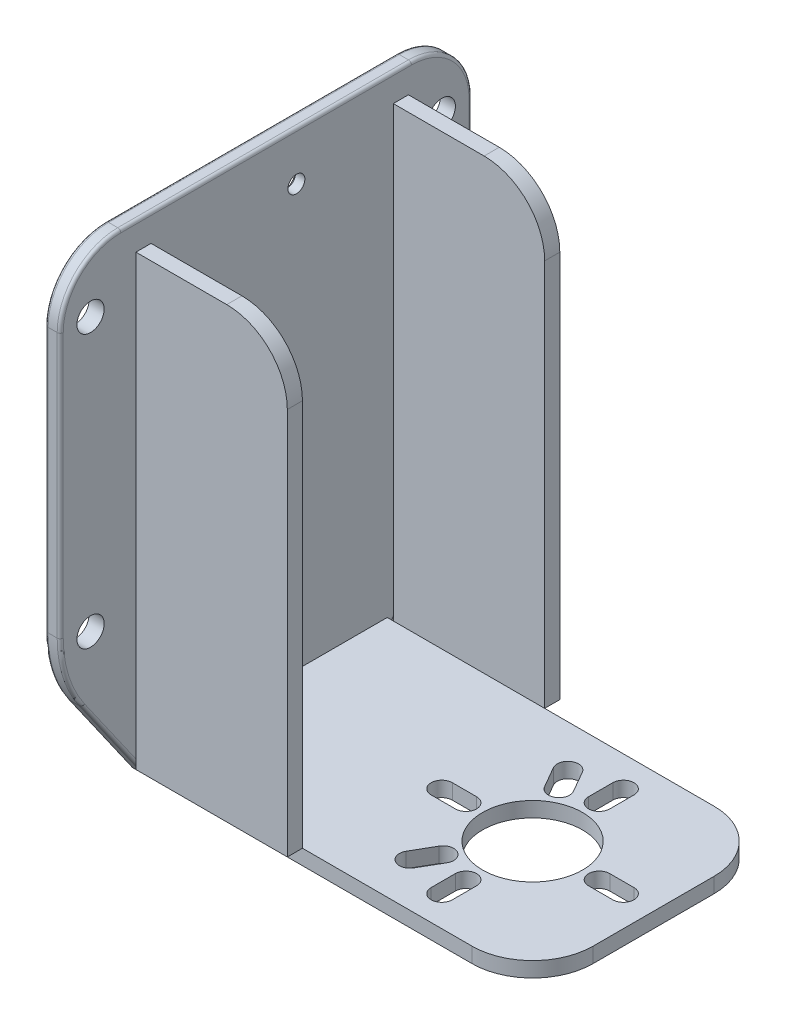
SolidWorks part; units mm, degrees
ref_plane "前视基准面" through (0, 0, 0) normal (0, 0, 1) x (1, 0, 0)
ref_plane "上视基准面" through (0, 0, 0) normal (0, 1, 0) x (1, 0, 0)
ref_plane "右视基准面" through (0, 0, 0) normal (1, 0, 0) x (0, 0, -1)
sketch "草图1" plane through (0, 0, 0) normal (0, 1, 0) x (1, 0, 0)
  line L0 (-53.6479, 52.8766) -> (-53.6479, 12.8766) construction
  line L1 (-77.6479, 52.8766) -> (-13.6479, 52.8766)
  line L2 (-77.6479, 52.8766) -> (-77.6479, 12.8766)
  line L3 (-77.6479, 12.8766) -> (-13.6479, 12.8766)
  line L4 (-13.6479, 52.8766) -> (-13.6479, 12.8766)
  line L5 (-18.6479, 32.8766) -> (-22.6479, 32.8766) construction
  line L6 (-18.6479, 31.1266) -> (-22.6479, 31.1266)
  line L7 (-18.6479, 34.6266) -> (-22.6479, 34.6266)
  line L8 (-33.6479, 17.8766) -> (-33.6479, 21.8766) construction
  line L9 (-35.3979, 17.8766) -> (-35.3979, 21.8766)
  line L10 (-31.8979, 17.8766) -> (-31.8979, 21.8766)
  line L11 (-48.6479, 32.8766) -> (-44.6479, 32.8766) construction
  line L12 (-48.6479, 34.6266) -> (-44.6479, 34.6266)
  line L13 (-48.6479, 31.1266) -> (-44.6479, 31.1266)
  line L14 (-33.6479, 47.8766) -> (-33.6479, 43.8766) construction
  line L15 (-31.8979, 47.8766) -> (-31.8979, 43.8766)
  line L16 (-35.3979, 47.8766) -> (-35.3979, 43.8766)
  line L17 (-41.1479, 20.1362) -> (-39.1479, 23.6003) construction
  line L18 (-42.6635, 21.0112) -> (-40.6635, 24.4753)
  line L19 (-39.6324, 19.2612) -> (-37.6324, 22.7253)
  line L20 (-40.9314, 45.992) -> (-38.9314, 42.5279) construction
  line L21 (-39.4159, 46.867) -> (-37.4159, 43.4029)
  line L22 (-42.447, 45.117) -> (-40.447, 41.6529)
  circle A0 centre (-33.6479, 32.8766) radius 8.25
  arc A1 (-35.3979, 17.8766) -> (-31.8979, 17.8766) centre (-33.6479, 17.8766) ccw
  arc A2 (-18.6479, 31.1266) -> (-18.6479, 34.6266) centre (-18.6479, 32.8766) ccw
  arc A3 (-22.6479, 34.6266) -> (-22.6479, 31.1266) centre (-22.6479, 32.8766) ccw
  arc A4 (-31.8979, 21.8766) -> (-35.3979, 21.8766) centre (-33.6479, 21.8766) ccw
  arc A5 (-48.6479, 34.6266) -> (-48.6479, 31.1266) centre (-48.6479, 32.8766) ccw
  arc A6 (-44.6479, 31.1266) -> (-44.6479, 34.6266) centre (-44.6479, 32.8766) ccw
  arc A7 (-31.8979, 47.8766) -> (-35.3979, 47.8766) centre (-33.6479, 47.8766) ccw
  arc A8 (-35.3979, 43.8766) -> (-31.8979, 43.8766) centre (-33.6479, 43.8766) ccw
  arc A9 (-42.6635, 21.0112) -> (-39.6324, 19.2612) centre (-41.1479, 20.1362) ccw
  arc A10 (-37.6324, 22.7253) -> (-40.6635, 24.4753) centre (-39.1479, 23.6003) ccw
  arc A11 (-39.4159, 46.867) -> (-42.447, 45.117) centre (-40.9314, 45.992) ccw
  arc A12 (-40.447, 41.6529) -> (-37.4159, 43.4029) centre (-38.9314, 42.5279) ccw
  point P12 (-20.6479, 32.8766)
  point P20 (-33.6479, 19.8766)
  point P27 (-46.6479, 32.8766)
  point P34 (-33.6479, 45.8766)
  point P39 (-33.6479, 32.8766)
  point P41 (-40.1479, 21.8683)
  point P48 (-39.9314, 44.2599)
  point P53 (-33.5758, 33.0016)
  dimension "D2" = 16.5
  dimension "D3" = 20
  dimension "D1" = 64
  dimension "D4" = 4
  dimension "D6" = 40
  dimension "D7" = 40
  dimension "D5" = 11
  dimension "D8" = 3.5
  dimension "D11" = 20
  dimension "D9" = 4
  dimension "D10" = 3
extrude "凸台-拉伸1" add sketch "草图1" along normal blind 2.5
sketch "草图2" plane through (-77.6479, 0, 0) normal (-1, 0, 0) x (0, 0, 1)
  line L0 (-66.8807, 20) -> (-52.8766, 0)
  line L1 (-66.8807, 20) -> (1.1276, 20)
  line L2 (-52.8766, 0) -> (-12.8766, 0)
  line L3 (1.1276, 20) -> (-12.8766, 0)
  line L4 (-52.8766, 0) -> (-12.8766, 0) construction
  dimension "D1" = 20
  dimension "D2" = 55
  dimension "D3" = 55
  dimension "D4" = 68.0083
extrude "凸台-拉伸2" add sketch "草图2" along normal blind 2.5
sketch "草图6" plane through (0, 20, 0) normal (0, 1, 0) x (1, 0, 0)
  line L1 (-77.6479, 66.8807) -> (-80.1479, 66.8807)
  line L2 (-77.6479, 66.8807) -> (-77.6479, -1.1276)
  line L3 (-77.6479, -1.1276) -> (-80.1479, -1.1276)
  line L4 (-80.1479, 66.8807) -> (-80.1479, -1.1276)
extrude "凸台-拉伸3" add sketch "草图6" along normal blind 60
sketch "草图7" plane through (-77.6479, 0, 0) normal (1, 0, 0) x (0, 0, -1)
  line L0 (66.8807, 80) -> (66.8807, 20) construction
  line L1 (-1.1276, 80) -> (-1.1276, 20) construction
  line L2 (-1.1276, 80) -> (66.8807, 80) construction
  line L5 (52.8766, 2.5) -> (52.8766, 80) construction
  circle A0 centre (61.8807, 25) radius 2.25
  circle A1 centre (3.8807, 25) radius 2.25
  circle A2 centre (61.8807, 70) radius 2.25
  circle A3 centre (3.8807, 70) radius 2.25
  dimension "D1" = 4.5
  dimension "D3" = 58
  dimension "D4" = 5
  dimension "D5" = 5.0083
  dimension "D6" = 45
  dimension "D7" = 10
extrude "切除-拉伸1" cut sketch "草图7" against normal through all
fillet "圆角1" radius 10 2 edges at (-13.6479, 1.25, -12.8766) (-13.6479, 1.25, -52.8766)
fillet "圆角2" radius 20 2 edges at (-78.8979, 20, -66.8807) (-78.8979, 20, 1.1276)
fillet "圆角4" radius 10 2 edges at (-78.8979, 80, 1.1276) (-78.8979, 80, -66.8807)
fillet "圆角12" radius 0.5 9 edges at (-77.6479, 7.4172, -58.0702) (-77.6479, 20.2919, -65.9551) (-77.6479, 48.153, -66.8807) (-77.6479, 77.0711, -63.9518) (-77.6479, 80, -32.8766) (-77.6479, 77.0711, -1.8014) (-77.6479, 7.4172, -7.683) (-77.6479, 20.2919, 0.2019) (-77.6479, 48.153, 1.1276)
fillet "圆角13" radius 0.5 9 edges at (-80.1479, 7.4172, -58.0702) (-80.1479, 20.2919, -65.9551) (-80.1479, 48.153, -66.8807) (-80.1479, 77.0711, -63.9518) (-80.1479, 80, -32.8766) (-80.1479, 77.0711, -1.8014) (-80.1479, 7.4172, -7.683) (-80.1479, 20.2919, 0.2019) (-80.1479, 48.153, 1.1276)
sketch "草图8" plane through (0, 2.5, 0) normal (0, 1, 0) x (1, 0, 0)
  line L0 (-77.6479, 52.8766) -> (-77.6479, 12.8766) construction
  line L1 (-76.6479, 52.8766) -> (-51.6479, 52.8766)
  line L2 (-76.6479, 52.8766) -> (-76.6479, 55.3766)
  line L3 (-76.6479, 55.3766) -> (-51.6479, 55.3766)
  line L4 (-51.6479, 52.8766) -> (-51.6479, 55.3766)
  line L5 (-76.6479, 12.8766) -> (-51.6479, 12.8766)
  line L6 (-76.6479, 12.8766) -> (-76.6479, 10.3766)
  line L7 (-76.6479, 10.3766) -> (-51.6479, 10.3766)
  line L8 (-51.6479, 12.8766) -> (-51.6479, 10.3766)
  dimension "D1" = 25
  dimension "D2" = 2.5
  dimension "D3" = 1
  dimension "D4" = 1
extrude "凸台-拉伸5" add sketch "草图8" along normal blind 74 separate body
fillet "圆角14" radius 10 1 edges at (-51.6479, 76.5, -54.1266)
fillet "圆角15" radius 10 1 edges at (-51.6479, 76.5, -11.6266)
hole_wizard "#3 平头机械螺钉的锥形沉头孔 (100)1" positions "草图14" profile "草图13" countersink size "#3" standard "Ansi Inch" end condition through all
sketch "草图14" plane through (-80.1479, 0, 0) normal (-1, 0, 0) x (0, 0, 1)
  line L1 (-52.8766, 2.5) -> (-52.8766, 80) construction
  line L3 (-56.8807, 80) -> (-8.8724, 80) construction
  point P0 (-37.8766, 72)
  dimension "D1" = 15
  dimension "D2" = 8
sketch "草图13" plane through (-80.1479, 72, -37.8766) normal (0, 1, 0) x (0, 0, 1)
  line L0 (0, 0) -> (0, 66.5)
  line L1 (0, 66.5) -> (1.397, 66.5)
  line L2 (1.397, 66.5) -> (1.397, 0.9484)
  line L3 (1.397, 0.9484) -> (2.5273, 0)
  line L5 (2.5273, 0) -> (0, 0)
  line L6 (-1.397, 0.9484) -> (-2.5273, 0) construction
  line L11 (0, -6.35) -> (0, 107.95) construction
  dimension "通孔孔直径" = 2.794
  dimension "通孔孔深度" = 66.5
  dimension "近端锥形沉头孔直径" = 5.0546
  dimension "近端锥形沉头孔角度" = 100
